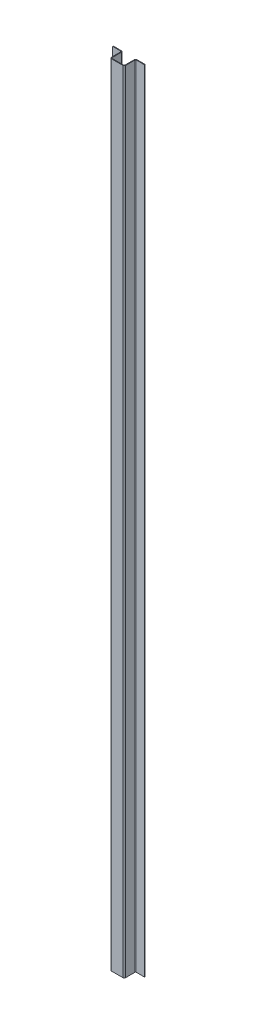
SolidWorks part; units mm, degrees
note: The reader was unsure of these and kept them because the rebuilt part matched: flange length of "Edge-Flange1", "Edge-Flange2".
material "Galvanized Steel"
ref_plane "Front Plane" through (0, 0, 0) normal (0, 0, 1) x (1, 0, 0)
ref_plane "Top Plane" through (0, 0, 0) normal (0, 1, 0) x (1, 0, 0)
ref_plane "Right Plane" through (0, 0, 0) normal (1, 0, 0) x (0, 0, -1)
sketch "Sketch1" plane through (0, 0, 0) normal (0, 0, 1) x (1, 0, 0)
  line L1 (22.5, -1254) -> (-22.5, -1254)
  line L2 (22.5, -1254) -> (22.5, 1254)
  line L3 (22.5, 1254) -> (-22.5, 1254)
  line L4 (-22.5, -1254) -> (-22.5, 1254)
  line L5 (22.5, -1254) -> (-22.5, 1254) construction
  line L6 (22.5, 1254) -> (-22.5, -1254) construction
  point P0 (0, 0)
  dimension "D1" = 2508
  dimension "D2" = 45
base flange "Base-Flange1" sketch "Sketch1" thickness 2 reverse thickness direction no parameters "D1"=8
edge flange "Edge-Flange1" sketch "Sketch10" flange profiles "Sketch10", "Sketch11" flange angle 90 flange length 38 flange position material inside bend radius 2.5 thickness 2 relief rectangular parameters "D6"=10, "D8"=1
sketch "Sketch10" plane through (22.5, 0, -2) normal (1, 0, 0) x (0, -1, 0)
  line L0 (1254, 0) -> (-1254, 0) construction
  line L1 (1254, 0) -> (-1254, 0)
  line L2 (-1254, 0) -> (-1254, 36)
  line L3 (-1254, 36) -> (1254, 36)
  line L4 (1254, 36) -> (1254, 0)
sketch "Sketch11" plane through (-22.5, 0, -2) normal (-1, 0, 0) x (0, 1, 0)
  line L0 (1254, 0) -> (-1254, 0) construction
  line L1 (1254, 0) -> (-1254, 0)
  line L2 (-1254, 0) -> (-1254, 36)
  line L3 (-1254, 36) -> (1254, 36)
  line L4 (1254, 36) -> (1254, 0)
bend "EdgeBend1" bend radius 2.5 bend angle 90 parameters "D5"=1
bend "EdgeBend2" bend radius 2.5 bend angle 90 parameters "D5"=2
edge flange "Edge-Flange2" sketch "Sketch16" flange profiles "Sketch16", "Sketch17" flange angle 90 flange length 30 flange position material inside bend radius 2.5 thickness 2 relief rectangular parameters "D6"=10, "D8"=1
sketch "Sketch16" plane through (-22.5, 0, -38) normal (0, 0, -1) x (0, -1, 0)
  line L2 (-1254, 0) -> (-1254, 28)
  line L3 (-1254, 28) -> (1254, 28)
  line L4 (1254, 28) -> (1254, 0)
  line L7 (-1254, 0) -> (1254, 0) construction
  line L8 (-1254, 0) -> (1254, 0)
sketch "Sketch17" plane through (22.5, 0, -38) normal (0, 0, -1) x (0, 1, 0)
  line L0 (-1254, 0) -> (1254, 0) construction
  line L1 (-1254, 0) -> (1254, 0)
  line L2 (-1254, 0) -> (-1254, 28)
  line L3 (-1254, 28) -> (1254, 28)
  line L4 (1254, 28) -> (1254, 0)
bend "EdgeBend3" bend radius 2.5 bend angle 90 parameters "D5"=3
bend "EdgeBend4" bend radius 2.5 bend angle 90 parameters "D5"=4
sketch "Bend-Lines1" [suppressed] plane through (0, 0, 0) normal (0, 1, 0) x (1, 0, 0)
sketch "Bounding-Box1" [suppressed] plane through (0, 0, 0) normal (0, 1, 0) x (1, 0, 0)
sheet metal parameters "Sheet-Metal8" thickness 2 parameters "D1"=8
flat pattern "Flat-Pattern8" [suppressed]
sketch "Bend-Lines2" plane through (0, 0, 0) normal (0, 1, 0) x (1, 0, 0)
sketch3d "Bounding-Box2" [suppressed]
  line L0 (-20, 1200, 0) -> (-20, -1200, 0) construction
  line L1 (20, 1200, 0) -> (20, -1200, 0) construction
  line L2 (-20, 1200, 0) -> (20, 1200, 0) construction
  line L3 (-20, -1200, 0) -> (20, -1200, 0) construction
sheet metal parameters "Sheet-Metal9" thickness 2 parameters "D1"=8
flat pattern "Flat-Pattern8"
sketch "Bend-Lines2" plane through (0, 0, 0) normal (0, 0, 1) x (1, 0, 0)
  line L0 (-18.2489, 1200) -> (-18.2489, -1200) construction
  line L1 (18.2489, -1200) -> (18.2489, 1200) construction
  line L2 (-18.2489, 1200) -> (-18.2489, -1200) construction
  line L3 (18.2489, -1200) -> (18.2489, 1200) construction
sketch3d "Bounding-Box2" [suppressed]
  line L0 (56.4978, 1200, 0) -> (56.4978, -1200, 0) construction
  line L1 (-56.4978, 1200, 0) -> (-56.4978, -1200, 0) construction
  line L2 (56.4978, 1200, 0) -> (-56.4978, 1200, 0) construction
  line L3 (56.4978, -1200, 0) -> (-56.4978, -1200, 0) construction
bend of the flat pattern "Flatten-<EdgeBend1>1"
bend of the flat pattern "Flatten-<EdgeBend2>1"
sheet metal parameters "Sheet-Metal10" thickness 2 parameters "D1"=8
flat pattern "Flat-Pattern8"
sketch "Bend-Lines2" plane through (0, 0, 0) normal (0, 0, 1) x (1, 0, 0)
  line L0 (-20.7489, 1254) -> (-20.7489, -1254) construction
  line L1 (20.7489, -1254) -> (20.7489, 1254) construction
  line L2 (-20.7489, 1254) -> (-20.7489, -1254) construction
  line L3 (20.7489, -1254) -> (20.7489, 1254) construction
  line L4 (55.2467, -1254) -> (55.2467, 1254) construction
  line L5 (-55.2467, 1254) -> (-55.2467, -1254) construction
  line L6 (55.2467, -1254) -> (55.2467, 1254) construction
  line L7 (-55.2467, 1254) -> (-55.2467, -1254) construction
sketch3d "Bounding-Box2" [suppressed]
  line L0 (83.4956, 1254, 0) -> (83.4956, -1254, 0) construction
  line L1 (-83.4956, 1254, 0) -> (-83.4956, -1254, 0) construction
  line L2 (83.4956, 1254, 0) -> (-83.4956, 1254, 0) construction
  line L3 (83.4956, -1254, 0) -> (-83.4956, -1254, 0) construction
bend of the flat pattern "Flatten-<EdgeBend1>1"
bend of the flat pattern "Flatten-<EdgeBend2>1"
bend of the flat pattern "Flatten-<EdgeBend3>1"
bend of the flat pattern "Flatten-<EdgeBend4>1"
